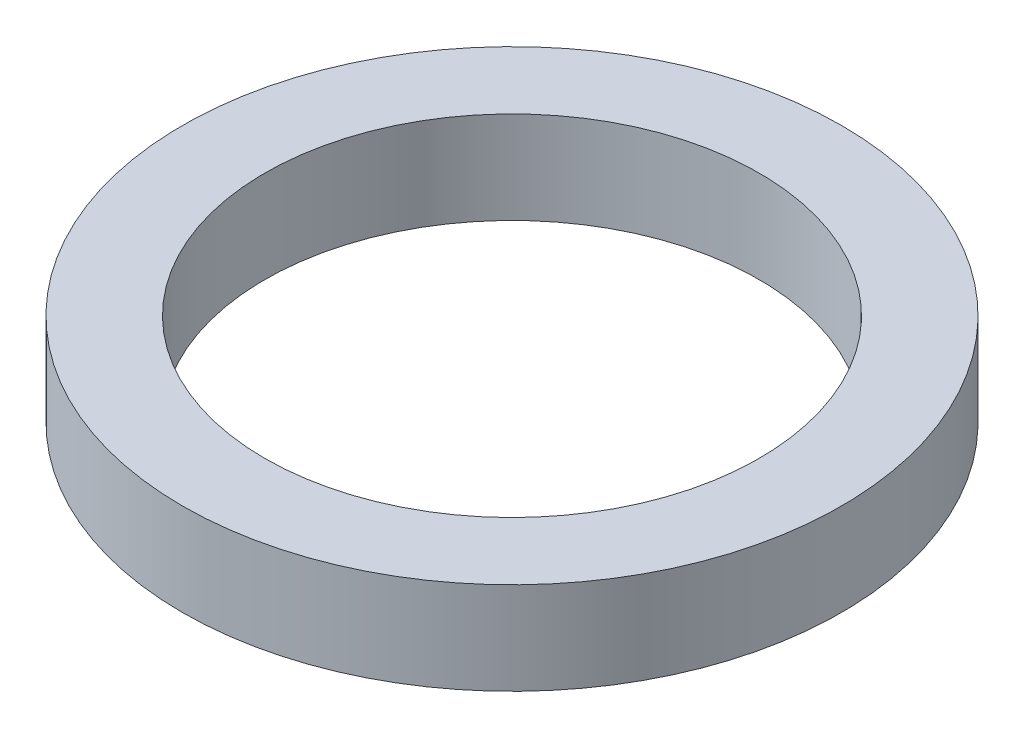
SolidWorks part; units mm, degrees
ref_plane "Front Plane" through (0, 0, 0) normal (0, 0, 1) x (1, 0, 0)
ref_plane "Top Plane" through (0, 0, 0) normal (0, 1, 0) x (1, 0, 0)
ref_plane "Right Plane" through (0, 0, 0) normal (1, 0, 0) x (0, 0, -1)
sketch "Sketch1" plane through (0, 0, 0) normal (0, 1, 0) x (1, 0, 0)
  circle A0 centre (0, 0) radius 50
  dimension "FLANGE_OD" = 100
extrude "Boss-Extrude1" add sketch "Sketch1" along normal blind 14
sketch "Sketch2" plane through (0, 0, 0) normal (0, 1, 0) x (1, 0, 0)
  circle A0 centre (0, 0) radius 37.5
  dimension "BORE_D" = 75
extrude "Cut-Extrude1" cut sketch "Sketch2" along normal through all
sketch "Sketch3" plane through (0, 14, 0) normal (0, 1, 0) x (1, 0, 0)
  circle A0 centre (0, 0) radius 22.1006 construction
  circle A1 centre (-22.1006, 0) radius 1.8552
  dimension "BOLT_D" = 3.7105
  dimension "BOLT_PCD" = 44.2013
extrude "Cut-Extrude2" cut sketch "Sketch3" against normal blind 13.0431 rebuild error yes
pattern_circular "CirPattern1" count 4 over 360 rebuild error yes
